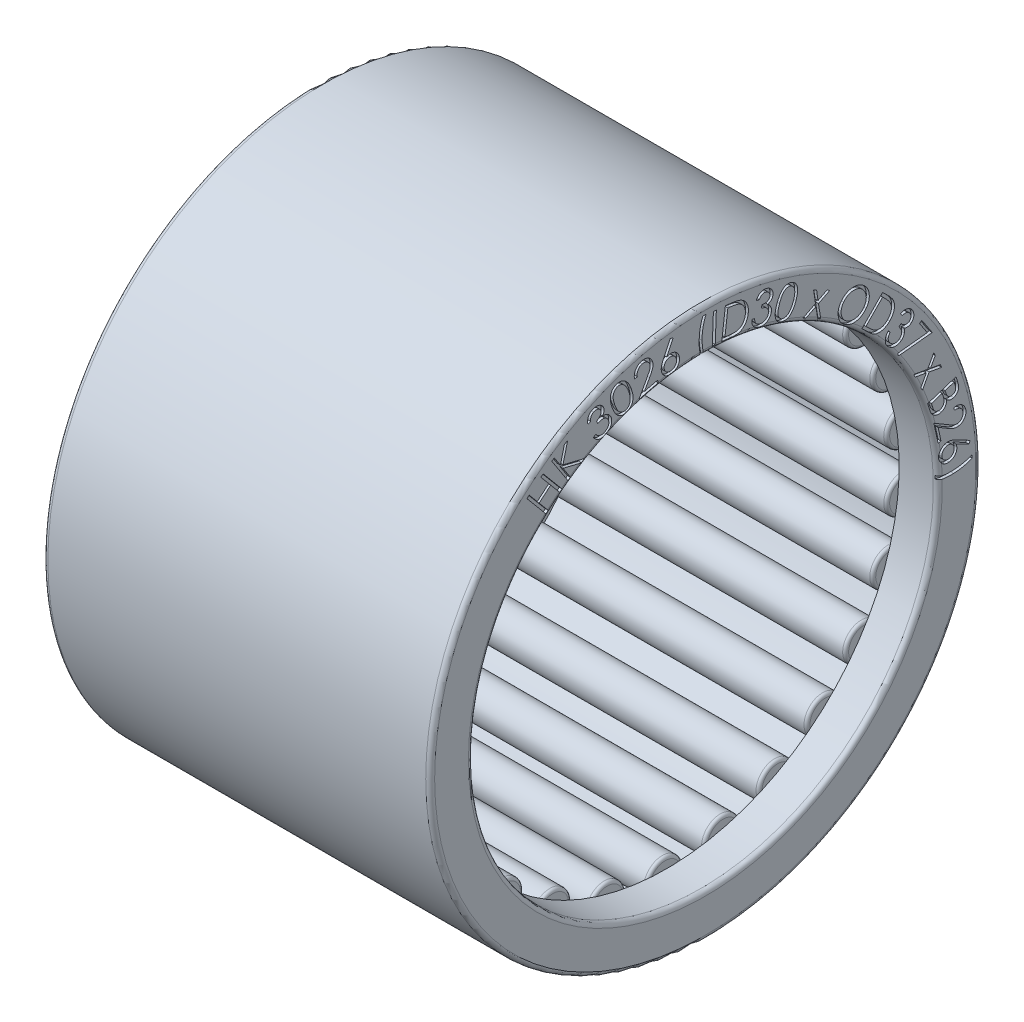
SolidWorks part; units mm, degrees
material "Plain Carbon Steel"
ref_plane "Front Plane" through (0, 0, 0) normal (0, 0, 1) x (1, 0, 0)
ref_plane "Top Plane" through (0, 0, 0) normal (0, 1, 0) x (1, 0, 0)
ref_plane "Right Plane" through (0, 0, 0) normal (1, 0, 0) x (0, 0, -1)
sketch "Sketch1" plane through (0, 0, 0) normal (0, 0, 1) x (1, 0, 0)
  line L0 (0, 0) -> (95.772, 0) construction
  line L1 (0, 18.5) -> (0, 15.625)
  line L2 (0, 18.5) -> (26, 18.5)
  line L3 (26, 18.5) -> (26, 15.625)
  line L4 (26, 15.625) -> (23.4, 15.625)
  line L5 (2.6, 15.625) -> (2.6, 17.5)
  line L6 (2.6, 17.5) -> (23.4, 17.5)
  line L9 (13, 18.5) -> (13, 7.5992) construction
  line L12 (23.4, 15.625) -> (23.4, 17.5)
  line L13 (2.6, 15.625) -> (0, 15.625)
  point P15 (13, 15)
  dimension "D1" = 26
  dimension "D2" = 37
  dimension "D3" = 31.25
  dimension "D4" = 20.8
  dimension "D5" = 35
revolve "Revolve1" add sketch "Sketch1" angle 360 about L0
fillet "Fillet1" radius 0.3 4 edges at (0, 0, 18.5) (26, 0, 15.625) (26, 0, 18.5) (0, 0, 15.625)
sketch "Sketch2" plane through (26, 0, 0) normal (1, 0, 0) x (0, 0, -1)
  circle A0 centre (0, 0) radius 15.8618 construction
  text T0 "HK 3026 (ID30 x OD37 x B26)" font "Century Gothic" height 2
extrude "Extrude1" cut sketch "Sketch2" against normal blind 0.2
sketch "Sketch3" plane through (0, 0, 0) normal (0, 0, 1) x (1, 0, 0)
  line L0 (-3.8597, 16.255) -> (29.1986, 16.255) construction
  line L1 (23.4, 15.625) -> (23.4, -15.625) construction
  line L2 (2.7, 16.255) -> (23.3, 16.255)
  line L3 (2.7, 16.255) -> (2.7, 17.305)
  line L4 (2.9, 17.505) -> (23.1, 17.505)
  line L5 (23.3, 16.255) -> (23.3, 17.305)
  line L6 (2.6, -17.5) -> (2.6, 17.5) construction
  arc A0 (23.1, 17.505) -> (23.3, 17.305) centre (23.1, 17.305) cw
  arc A1 (2.7, 17.305) -> (2.9, 17.505) centre (2.9, 17.305) cw
  dimension "D5" = 0.2
  dimension "D1" = 17.505
  dimension "D2" = 2.5
  dimension "D3" = 0.1
  dimension "D4" = 0.1
revolve "Revolve2" add sketch "Sketch3" angle 360 about L0
pattern_circular "CirPattern1" count 26 over 360 about axis through (0, 0, 0) along (-1, 0, 0) of "Revolve2"
